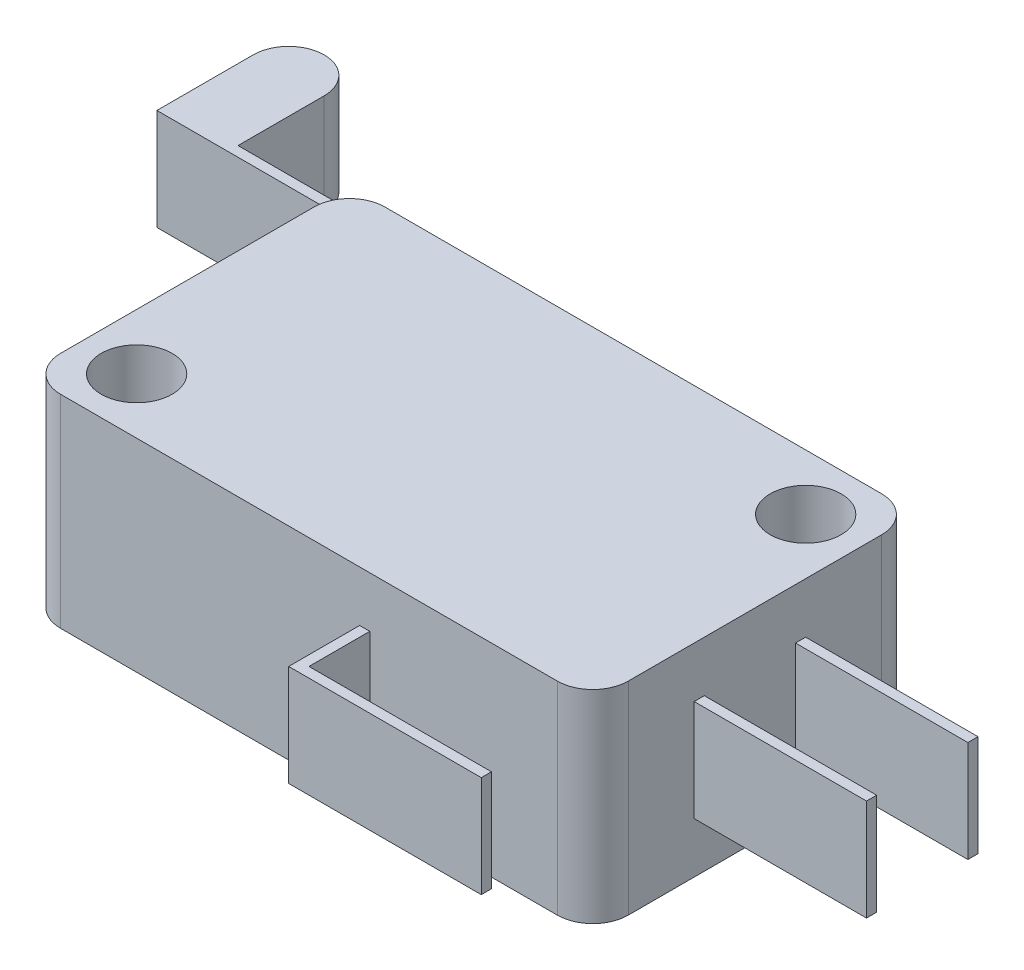
SolidWorks part; units mm, degrees
ref_plane "Front Plane" through (0, 0, 0) normal (0, 0, 1) x (1, 0, 0)
ref_plane "Top Plane" through (0, 0, 0) normal (0, 1, 0) x (1, 0, 0)
ref_plane "Right Plane" through (0, 0, 0) normal (1, 0, 0) x (0, 0, -1)
sketch "Sketch1" plane through (0, 0, 0) normal (0, 1, 0) x (1, 0, 0)
  line L0 (0, 0) -> (28, 0)
  line L1 (28, 0) -> (28, 16)
  line L2 (28, 16) -> (0, 16)
  line L3 (0, 16) -> (0, 0)
  dimension "D1" = 16
  dimension "D2" = 28
extrude "Boss-Extrude1" add sketch "Sketch1" along normal blind 10
sketch "Sketch3" plane through (0, 0, -16) normal (0, 0, -1) x (-1, 0, 0)
  line L0 (-28, 5) -> (-17, 5)
  line L1 (-28, 10) -> (-28, 0) construction
  line L2 (-17, 5) -> (-17, 7.5)
  line L3 (-17, 7.5) -> (-16.5, 7.5)
  line L4 (-16.5, 7.5) -> (-16.5, 2.5)
  line L5 (-16.5, 2.5) -> (-17, 2.5)
  line L6 (-17, 2.5) -> (-17, 5)
  dimension "D1" = 11
  dimension "D2" = 0.5
  dimension "D3" = 2.5
  dimension "D4" = 2.5
extrude "Boss-Extrude2" add sketch "Sketch3" along normal blind 1.5 contours L6 L5 L4 L3 L2 region at (16.75, 5, -16)
sketch "Sketch4" plane through (16.5, 0, 0) normal (-1, 0, 0) x (0, 0, 1)
  line L0 (-17.5, 2.5) -> (-16, 2.5) construction
  line L1 (-17.5, 7.5) -> (-17, 7.5)
  line L2 (-17.5, 7.5) -> (-17.5, 2.5)
  line L3 (-17.5, 2.5) -> (-17, 2.5)
  line L4 (-17, 7.5) -> (-17, 2.5)
  dimension "D1" = 0.5
extrude "Boss-Extrude3" add sketch "Sketch4" along normal blind 27
sketch "Sketch6" plane through (0, 2.5, 0) normal (0, -1, 0) x (1, 0, 0)
  line L1 (-10.5, -17.5) -> (-7, -17.5)
  line L2 (-10.5, -17.5) -> (-10.5, -23.5)
  line L3 (-10.5, -23.5) -> (-7, -23.5)
  line L4 (-7, -17.5) -> (-7, -23.5)
  dimension "D1" = 6
  dimension "D2" = 3.5
extrude "Boss-Extrude4" add sketch "Sketch6" against normal up to surface (5 mm away) up to face at (7.6667, 7.5, -16.8333)
fillet "Fillet1" radius 1.75 2 edges at (-7, 5, -23.5) (-10.5, 5, -23.5)
sketch "Sketch7" plane through (0, 0, 0) normal (0, 0, 1) x (1, 0, 0)
  line L0 (28, 5) -> (17, 5)
  line L1 (28, 10) -> (28, 0) construction
  line L2 (17, 5) -> (17, 7.5)
  line L3 (17, 7.5) -> (16.5, 7.5)
  line L4 (16.5, 7.5) -> (16.5, 2.5)
  line L5 (16.5, 2.5) -> (17, 2.5)
  line L6 (17, 2.5) -> (17, 5)
  dimension "D1" = 11
  dimension "D2" = 2.5
  dimension "D3" = 2.5
  dimension "D4" = 0.5
extrude "Boss-Extrude5" add sketch "Sketch7" along normal blind 3.5 contours L5 L6 L2 L3 L4 region at (16.75, 5, 0)
sketch "Sketch8" plane through (17, 0, 0) normal (1, 0, 0) x (0, 0, -1)
  line L0 (-3.5, 2.5) -> (0, 2.5) construction
  line L1 (-3.5, 7.5) -> (-3, 7.5)
  line L2 (-3.5, 7.5) -> (-3.5, 2.5)
  line L3 (-3.5, 2.5) -> (-3, 2.5)
  line L4 (-3, 7.5) -> (-3, 2.5)
  dimension "D1" = 0.5
extrude "Boss-Extrude6" add sketch "Sketch8" along normal blind 9
sketch "Sketch9" plane through (28, 0, 0) normal (1, 0, 0) x (0, 0, -1)
  line L0 (16, 5) -> (10.5, 5)
  line L1 (16, 10) -> (16, 0) construction
  line L2 (10.5, 5) -> (10.5, 7.5)
  line L3 (10.5, 7.5) -> (10, 7.5)
  line L4 (10, 7.5) -> (10, 2.5)
  line L5 (10, 2.5) -> (10.5, 2.5)
  line L6 (10.5, 2.5) -> (10.5, 5)
  line L7 (10, 5) -> (5.5, 5)
  line L8 (7.75, 5) -> (7.75, 3.7819)
  line L9 (5, 2.5) -> (5, 5)
  line L10 (5.5, 2.5) -> (5, 2.5)
  line L11 (5.5, 7.5) -> (5.5, 2.5)
  line L12 (5, 7.5) -> (5.5, 7.5)
  line L13 (5, 5) -> (5, 7.5)
  dimension "D1" = 5.5
  dimension "D2" = 2.5
  dimension "D3" = 2.5
  dimension "D4" = 0.5
  dimension "D5" = 4.5
extrude "Boss-Extrude7" add sketch "Sketch9" along normal blind 8.5 contours L5 L6 L2 L3 L4 | L13 L9 L10 L11 L12 region at (28, 5, -10.25) region at (28, 5, -5.25)
sketch "Sketch10" plane through (0, 10, 0) normal (0, 1, 0) x (1, 0, 0)
  line L0 (28, 16) -> (28, 13.25)
  line L1 (28, 0) -> (28, 16) construction
  line L2 (25.25, 16) -> (25.25, 15)
  line L3 (28, 16) -> (25.25, 16)
  line L4 (28, 16) -> (0, 16) construction
  line L5 (28, 13.25) -> (27, 13.25)
  line L6 (25.25, 15) -> (25.25, 13.25)
  line L7 (25.25, 13.25) -> (27, 13.25)
  circle A0 centre (25.25, 13.25) radius 1.75
  dimension "D1" = 2.75
  dimension "D2" = 1
  dimension "D4" = 2.75
  dimension "D5" = 1
extrude "Cut-Extrude1" cut sketch "Sketch10" against normal through all contours L6 A0 L7 | L7 A0 L6 region at (25.0024, 10, -13.0024) region at (25.9927, 10, -13.9927)
sketch "Sketch11" plane through (0, 10, 0) normal (0, 1, 0) x (1, 0, 0)
  line L0 (0, 0) -> (0, 2.75)
  line L1 (0, 16) -> (0, 0) construction
  line L2 (0, 0) -> (2.75, 0)
  line L3 (0, 0) -> (28, 0) construction
  line L4 (2.75, 0) -> (2.75, 1)
  line L5 (0, 2.75) -> (1, 2.75)
  line L6 (1, 2.75) -> (2.75, 2.75)
  line L7 (2.75, 2.75) -> (2.75, 1)
  circle A0 centre (2.75, 2.75) radius 1.75
  dimension "D1" = 2.75
  dimension "D2" = 2.75
  dimension "D3" = 1
  dimension "D4" = 1
extrude "Cut-Extrude2" cut sketch "Sketch11" against normal through all contours L7 A0 L6 | L6 A0 L7 region at (2.9976, 10, -2.9976) region at (2.0073, 10, -2.0073)
fillet "Fillet2" radius 1.75 4 edges at (28, 5, 0) (0, 5, -16) (28, 5, -16) (0, 5, 0)
